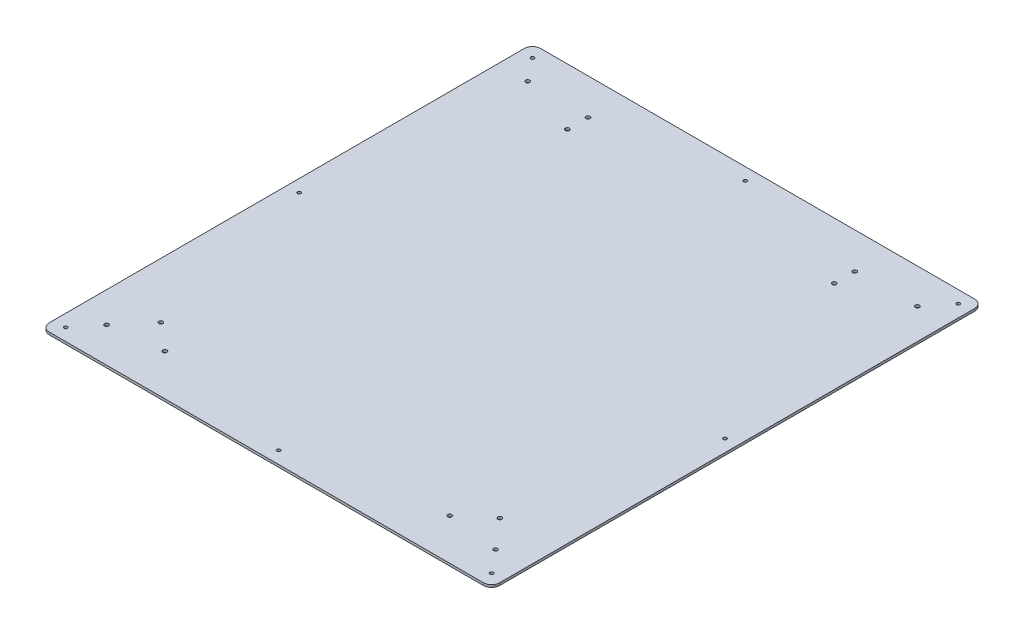
SolidWorks part; units mm, degrees
material "E-玻璃纤维"
ref_plane "前视基准面" through (0, 0, 0) normal (0, 0, 1) x (1, 0, 0)
ref_plane "上视基准面" through (0, 0, 0) normal (0, 1, 0) x (1, 0, 0)
ref_plane "右视基准面" through (0, 0, 0) normal (1, 0, 0) x (0, 0, -1)
other "Configuration Table"
sketch "草图1" plane through (0, 0, 0) normal (0, 1, 0) x (1, 0, 0)
  line L0 (-1000, 0) -> (49000, 0) construction
  line L1 (-265, -300) -> (265, -300)
  line L2 (-275, -290) -> (-275, 290)
  line L3 (-265, 300) -> (265, 300)
  line L4 (275, -290) -> (275, 290)
  line L5 (-275, -300) -> (275, 300) construction
  line L6 (-275, 300) -> (275, -300) construction
  line L7 (0, -1000) -> (0, 49000) construction
  line L8 (-260, -285) -> (260, -285) construction
  line L9 (260, -285) -> (260, 285) construction
  line L10 (260, 285) -> (-260, 285) construction
  line L11 (-260, 285) -> (-260, -285) construction
  arc A0 (265, 300) -> (275, 290) centre (265, 290) cw
  arc A1 (265, -300) -> (275, -290) centre (265, -290) ccw
  arc A2 (-265, -300) -> (-275, -290) centre (-265, -290) cw
  arc A3 (-275, 290) -> (-265, 300) centre (-265, 290) cw
  circle A16 centre (-260, 285) radius 2.1
  circle A18 centre (260, 285) radius 2.1
  circle A19 centre (260, -285) radius 2.1
  circle A20 centre (-260, -285) radius 2.1
  circle A21 centre (-260, 0) radius 2.1
  circle A22 centre (0, 285) radius 2.1
  circle A23 centre (260, 0) radius 2.1
  circle A24 centre (0, -285) radius 2.1
  point P0 (0, 0)
  line B0 (-238.2238, 257.3525) -> (-237.7762, -257.3525) construction
  line B1 (-237.7762, -257.3525) -> (237.3286, -257.3525) construction
  line B2 (237.3286, -257.3525) -> (237.7762, 257.3525) construction
  line B3 (237.7762, 257.3525) -> (-238.2238, 257.3525) construction
  line B4 (-238.2238, 257.3525) -> (237.3286, -257.3525) construction
  line B5 (237.7762, 257.3525) -> (-237.7762, -257.3525) construction
  circle B6 centre (206.7762, -221.6475) radius 2.5
  circle B7 centre (173.7762, -249.6475) radius 2.5
  circle B8 centre (-174.2238, -249.6475) radius 2.5
  circle B9 centre (-207.2238, -221.6475) radius 2.5
  circle B10 centre (-237.7762, -257.3525) radius 2.5
  circle B11 centre (237.3286, -257.3525) radius 2.5
  circle B12 centre (237.7762, 257.3525) radius 2.5
  circle B13 centre (162.6877, 230.8525) radius 2.5
  circle B14 centre (162.6877, 255.8525) radius 2.5
  circle B15 centre (-163.1353, 255.8525) radius 2.5
  circle B16 centre (-238.2238, 257.3525) radius 2.5
  circle B17 centre (-163.1353, 230.8525) radius 2.5
  dimension "D3" = 10
  dimension "D4" = 4.2
  dimension "D5" = 15
  dimension "D7" = 4.2
  dimension "D1" = 550
  dimension "D2" = 600
  dimension "D6" = 15
sketch_block_instance "块1-1"
sketch_block "块1"
base flange "基体-法兰1" sketch "草图1" thickness 3 reverse thickness direction no parameters "D1"=0.7366
sketch "折弯-线1" [suppressed] plane through (0, 0, 0) normal (0, 1, 0) x (1, 0, 0)
sketch "边界框1" [suppressed] plane through (0, 0, 0) normal (0, 1, 0) x (1, 0, 0)
sheet metal parameters "钣金6" thickness 3 parameters "D1"=0.7366
flat pattern "平板型式6" [suppressed]
sketch "折弯-线2" plane through (0, 0, 0) normal (0, 1, 0) x (1, 0, 0)
sketch3d "边界框2" [suppressed]
  line L0 (10, -590, 0) -> (10, 10, 0) construction
  line L1 (-540, -590, 0) -> (-540, 10, 0) construction
  line L2 (10, -590, 0) -> (-540, -590, 0) construction
  line L3 (10, 10, 0) -> (-540, 10, 0) construction
